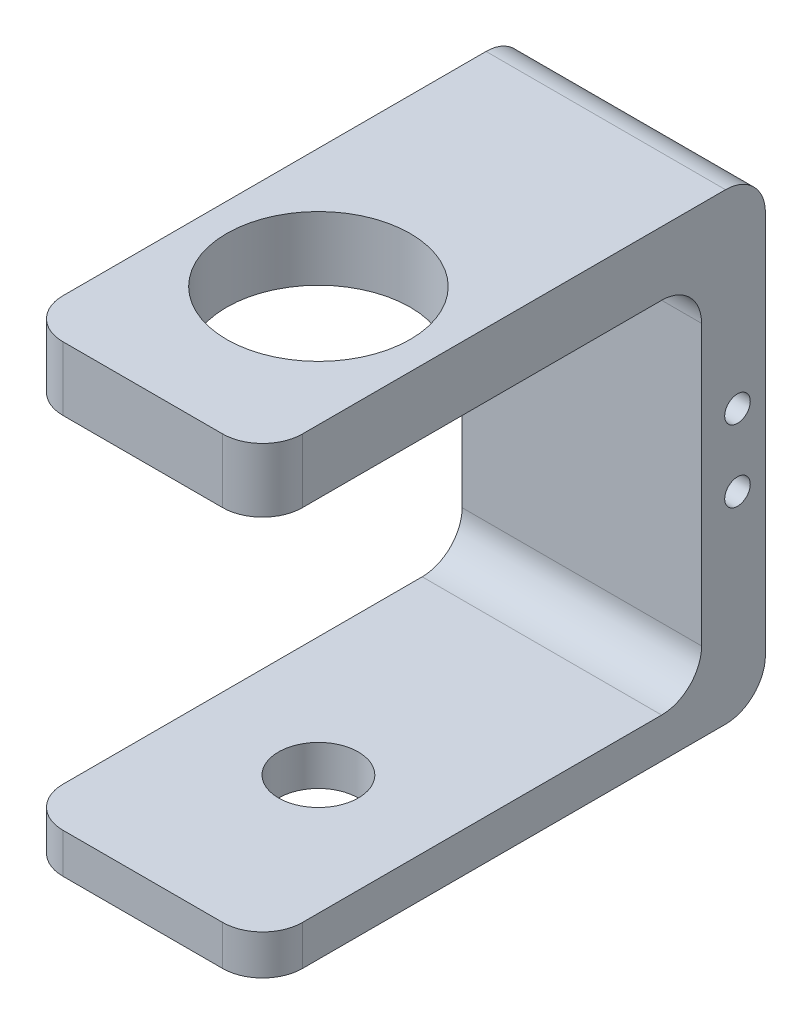
SolidWorks part; units mm, degrees
ref_plane "Front Plane" through (0, 0, 0) normal (0, 0, 1) x (1, 0, 0)
ref_plane "Top Plane" through (0, 0, 0) normal (0, 1, 0) x (1, 0, 0)
ref_plane "Right Plane" through (0, 0, 0) normal (1, 0, 0) x (0, 0, -1)
sketch "Sketch1" plane through (0, 0, 0) normal (1, 0, 0) x (0, 0, -1)
  line L0 (0, 0) -> (55, 0)
  line L1 (55, 0) -> (55, -45)
  line L2 (55, -45) -> (0, -45)
  line L3 (0, -45) -> (0, -50)
  line L4 (0, -50) -> (63, -50)
  line L5 (63, -50) -> (63, 8)
  line L6 (63, 8) -> (0, 8)
  line L7 (0, 8) -> (0, 0)
  dimension "D1" = 55
  dimension "D2" = 45
  dimension "D3" = 8
  dimension "D4" = 8
  dimension "D5" = 5
extrude "Boss-Extrude1" add sketch "Sketch1" along normal blind 30 contours L0 L1 L2 L3 L4 L5 L6 L7
sketch "Sketch2" plane through (0, 8, 0) normal (0, 1, 0) x (1, 0, 0)
  line L0 (30, 0) -> (0, 0) construction
  line L1 (30, 63) -> (0, 63) construction
  circle A0 centre (15, 22) radius 11.5
  point P2 (15, 0)
  dimension "D1" = 23
  dimension "D2" = 41
extrude "Cut-Extrude1" cut sketch "Sketch2" against normal up to next
sketch "Sketch3" plane through (0, -45, 0) normal (0, 1, 0) x (1, 0, 0)
  circle A0 centre (15, 22) radius 5
  circle A1 centre (15, 22) radius 11.5 construction
  dimension "D1" = 10
extrude "Cut-Extrude2" cut sketch "Sketch3" against normal up to next contours A0
sketch "Sketch4" plane through (30, 0, 0) normal (1, 0, 0) x (0, 0, -1)
  line L0 (63, -50) -> (63, 8) construction
  circle A2 centre (59.5, -25.5) radius 1.6
  circle A3 centre (59.5, -16.5) radius 1.6
  point P6 (63, -21)
  dimension "D1" = 9
  dimension "D4" = 3.2
  dimension "D2" = 3.5
  dimension "D3" = 4.5
extrude "Cut-Extrude3" cut sketch "Sketch4" against normal up to next contours A2 | A3 region at (30, -25.5, -59.5)
fillet "Fillet1" radius 5 6 edges at (15, -50, -63) (15, 8, -63) (0, -47.5, 0) (0, 4, 0) (30, -47.5, 0) (30, 4, 0)
fillet "Fillet2" radius 5 2 edges at (15, 0, -55) (15, -45, -55)
